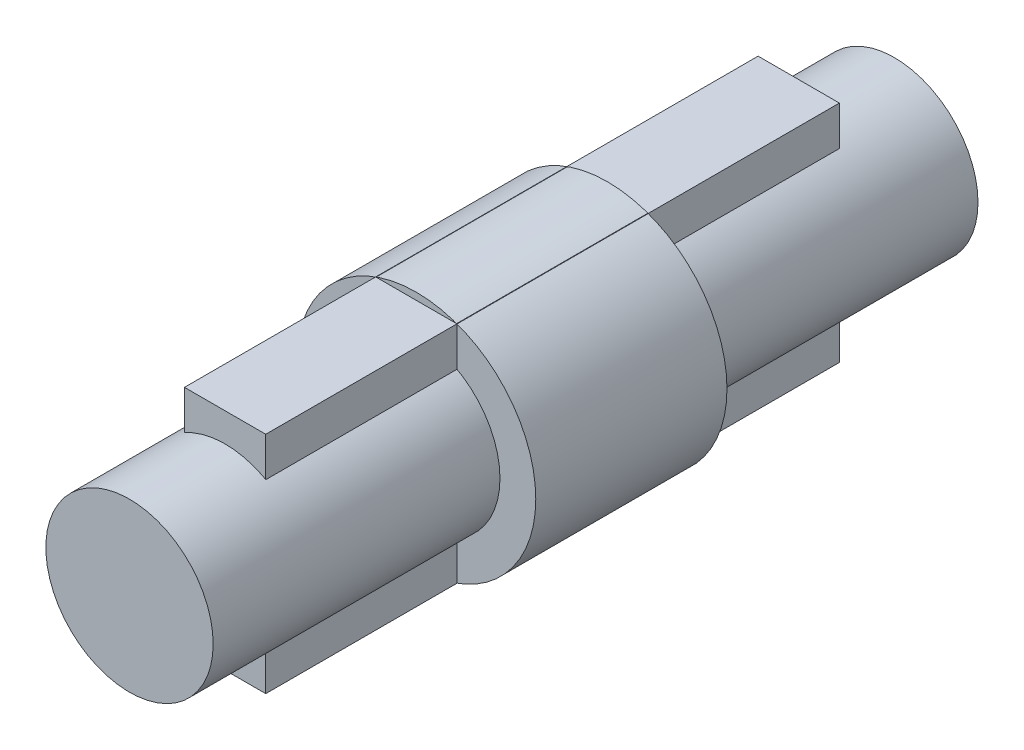
SolidWorks part; units mm, degrees
ref_plane "Front Plane" through (0, 0, 0) normal (0, 0, 1) x (1, 0, 0)
ref_plane "Top Plane" through (0, 0, 0) normal (0, 1, 0) x (1, 0, 0)
ref_plane "Right Plane" through (0, 0, 0) normal (1, 0, 0) x (0, 0, -1)
sketch "Sketch1" plane through (0, 0, 0) normal (0, 0, 1) x (1, 0, 0)
  line L0 (-0.85, 0) -> (0.85, 0)
  line L1 (0.85, 2.35) -> (0.85, -2.35)
  line L2 (0.85, 2.35) -> (-0.85, 2.35)
  line L3 (-0.85, 2.35) -> (-0.85, -2.35)
  line L4 (0.85, -2.35) -> (-0.85, -2.35)
  circle A0 centre (0, 0) radius 1.75
  circle A1 centre (0, 0) radius 2.499
  point P5 (0, 0)
  point P8 (0.85, 0)
  dimension "D1" = 3.5
  dimension "D2" = 1.7
  dimension "D3" = 4.7
extrude "Boss-Extrude1" add sketch "Sketch1" along normal mid plane 4 contours A1
extrude "Boss-Extrude2" add sketch "Sketch1<4>" along normal mid plane 12 separate body contours L1 A0 L3 L0 | A0 L1 L2 L3 | L3 A0 L1 L0 | A0 L3 L4 L1 region at (0, 0.8405, 0) region at (0, -0.8405, 0) region at (0, 2.0111, 0) region at (0, -2.0111, 0)
sketch "Sketch1<4>" plane through (0, 0, 0) normal (0, 0, 1) x (1, 0, 0) same geometry as "Sketch1"
extrude "Boss-Extrude3" add sketch "Sketch1<5>" along normal mid plane 16 separate body contours L1 A0 | L1 A0 L3 L0 | L3 A0 L1 L0 | L3 A0 region at (0, 0.8405, 0) region at (-1.2193, 0, 0) region at (0, -0.8405, 0) region at (1.2193, 0, 0)
sketch "Sketch1<5>" plane through (0, 0, 0) normal (0, 0, 1) x (1, 0, 0) same geometry as "Sketch1"
